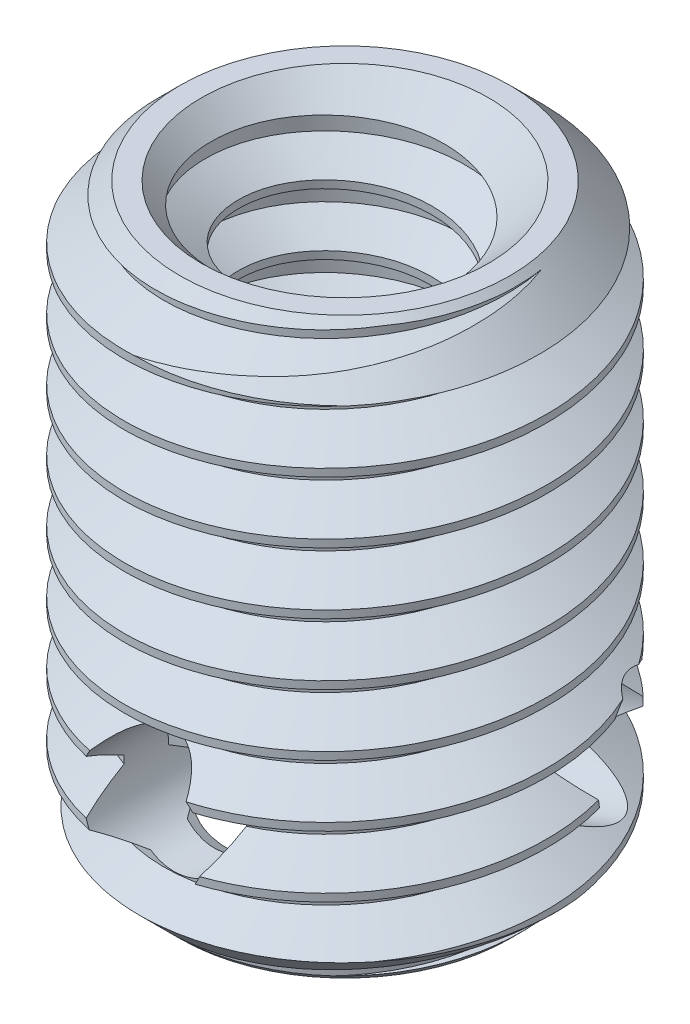
SolidWorks part; units mm, degrees
ref_plane "Front Plane" through (0, 0, 0) normal (0, 0, 1) x (1, 0, 0)
ref_plane "Top Plane" through (0, 0, 0) normal (0, 1, 0) x (1, 0, 0)
ref_plane "Right Plane" through (0, 0, 0) normal (1, 0, 0) x (0, 0, -1)
sketch "Sketch1" plane through (0, 0, 0) normal (0, 1, 0) x (1, 0, 0)
  line L0 (-2.1844, 0) -> (2.1844, 0) construction
  circle A0 centre (0, 0) radius 2.1844
  dimension "A" = 4.3688
extrude "Extrude1" add sketch "Sketch1" against normal blind 5.9436
sketch "Sketch2" plane through (0, 0, 0) normal (0, 1, 0) x (1, 0, 0)
  circle A2 centre (0, 0) radius 1.4224
  point P0 (-1.4224, 0)
  dimension "Thread OD" = 2.8448
curve "Helix/Spiral1" pitch 0.635 height 6.5786 radius 1.4224 centre (0, 0, 0) axis (0, -1, 0) start towards (0, 0, 1) parameters "Height"=6.5786, "Pitch"=0.635
sketch "Sketch3" plane through (0, 0, 0) normal (0, 0, 1) x (1, 0, 0)
  line L0 (-0.9412, 0.5953) -> (-0.9412, -0.0397) construction
  line L1 (-0.9412, -0.0397) -> (-1.4911, 0.2778) construction
  line L2 (-1.4911, 0.2778) -> (-0.9412, 0.5953) construction
  line L3 (-0.9412, 0.2778) -> (-1.01, 0.2778) construction
  line L4 (-1.01, 0.2778) -> (-1.3537, 0.2778) construction
  line L5 (-1.4224, 0.2778) -> (-1.4911, 0.2778) construction
  line L6 (-1.4224, 0.3175) -> (-1.4224, 0.2381) construction
  line L7 (-1.01, 0) -> (-1.01, 0.5556) construction
  line L8 (-1.4224, 0.2381) -> (-1.4224, 0) construction
  line L9 (-1.4224, 0) -> (-1.01, 0) construction
  line L10 (-1.3537, 0.3572) -> (-1.3537, 0.1984)
  line L11 (-1.3537, 0.1984) -> (-0.9756, -0.0198)
  line L12 (-0.9756, -0.0198) -> (-0.9756, 0.5755)
  line L13 (-0.9756, 0.5755) -> (-1.3537, 0.3572)
  line L14 (-1.4224, 0.2778) -> (-1.3537, 0.2778) construction
  point P18 (-0.9756, 0.2778)
  dimension "D1" = 0.635
  dimension "D2" = 0.0794
sketch "Sketch4" plane through (0, 0, 0) normal (0, 1, 0) x (-1, 0, 0)
  circle A0 centre (0, 0) radius 1.01
extrude "Extrude2" cut sketch "Sketch4" against normal through all
chamfer "Chamfer1" distance 0.4763 angle 45 2 edges at (0, 0, 1.01) (0, -5.9436, 1.01)
sweep "Cut-Sweep1" cut profiles "Sketch3" path "Helix/Spiral1" align with end faces yes
sketch "Sketch5" plane through (0, 0, 0) normal (0, 1, 0) x (1, 0, 0)
  circle A0 centre (0, 0) radius 2.1844 construction
  circle A1 centre (0, 0) radius 2.1844
  point P3 (-2.1844, 0)
curve "Helix/Spiral2" pitch 0.635 height 6.5786 radius 2.1844 centre (0, 0, 0) axis (0, -1, 0) start towards (0, 0, 1)
sketch "Sketch6" plane through (0, 0, 0) normal (0, 0, 1) x (1, 0, 0)
  line L0 (-2.2531, 0.5953) -> (-2.2531, -0.0397) construction
  line L1 (-2.2531, 0.5953) -> (-1.7032, 0.2778) construction
  line L2 (-1.7032, 0.2778) -> (-2.2531, -0.0397) construction
  line L3 (-2.1844, 0.5556) -> (-2.1844, 0) construction
  line L4 (-1.772, 0.3175) -> (-1.772, 0.2381)
  line L5 (-2.2188, 0.5755) -> (-1.772, 0.3175)
  line L6 (-2.2188, 0.5755) -> (-2.2188, -0.0198)
  line L7 (-2.2188, -0.0198) -> (-1.772, 0.2381)
  line L8 (-2.2531, 0.2778) -> (-2.1844, 0.2778) construction
  line L9 (-1.772, 0.2778) -> (-1.7032, 0.2778) construction
  point P13 (-2.2188, 0.2778)
  dimension "D1" = 0.635
  dimension "D2" = 0.0794
chamfer "Chamfer2" distance 0.4763 angle 45 2 edges at (0, -5.9436, 2.1844) (0, 0, 2.1844)
sweep "Cut-Sweep2" cut profiles "Sketch6" path "Helix/Spiral2" align with end faces yes
sketch "Sketch7" plane through (0, 0, 0) normal (0, 0, 1) x (1, 0, 0)
  line L0 (0, 0) -> (0, -4.0386) construction
  line L1 (1.7082, 0) -> (-1.7082, 0) construction
  line L2 (0, -4.6736) -> (0, -5.3086) construction
  line L3 (0, -5.3086) -> (0, -5.9436) construction
  line L4 (-1.7081, -5.9436) -> (1.7081, -5.9436) construction
  line L5 (0, -4.0386) -> (0, -4.6736) construction
  circle A0 centre (0, -4.6736) radius 0.635
  dimension "D1" = 1.27
extrude "Extrude3" cut sketch "Sketch7" along normal through all
ref_axis "Axis1" through (0, 1.8751, 0) along (0, -1, 0)
pattern_circular "CirPattern1" count 3 over 360 about axis through (0, 1.8751, 0) along (0, -1, 0) of "Extrude3"
equation "\"Height@Helix/Spiral1\" = \"Pitch@Helix/Spiral1\" + \"B@Extrude1\""
equation "\"D1@Sketch3\" = \"Pitch@Helix/Spiral1\""
equation "\"D2@Sketch3\" = \"D1@Sketch3\" / 8"
equation "\"D1@Chamfer1\" = \"Pitch@Helix/Spiral1\" * 6 / 8"
equation "\"D3@Helix/Spiral2\" = \"Height@Helix/Spiral1\""
equation "\"D4@Helix/Spiral2\" = \"Pitch@Helix/Spiral1\""
equation "\"D1@Sketch6\" = \"D4@Helix/Spiral2\""
equation "\"D2@Sketch6\" = \"D1@Sketch6\" / 8"
equation "\"D1@Chamfer2\" = \"D4@Helix/Spiral2\" * 6 / 8"
equation "\"D1@Sketch7\" = \"D4@Helix/Spiral2\" * 2"
